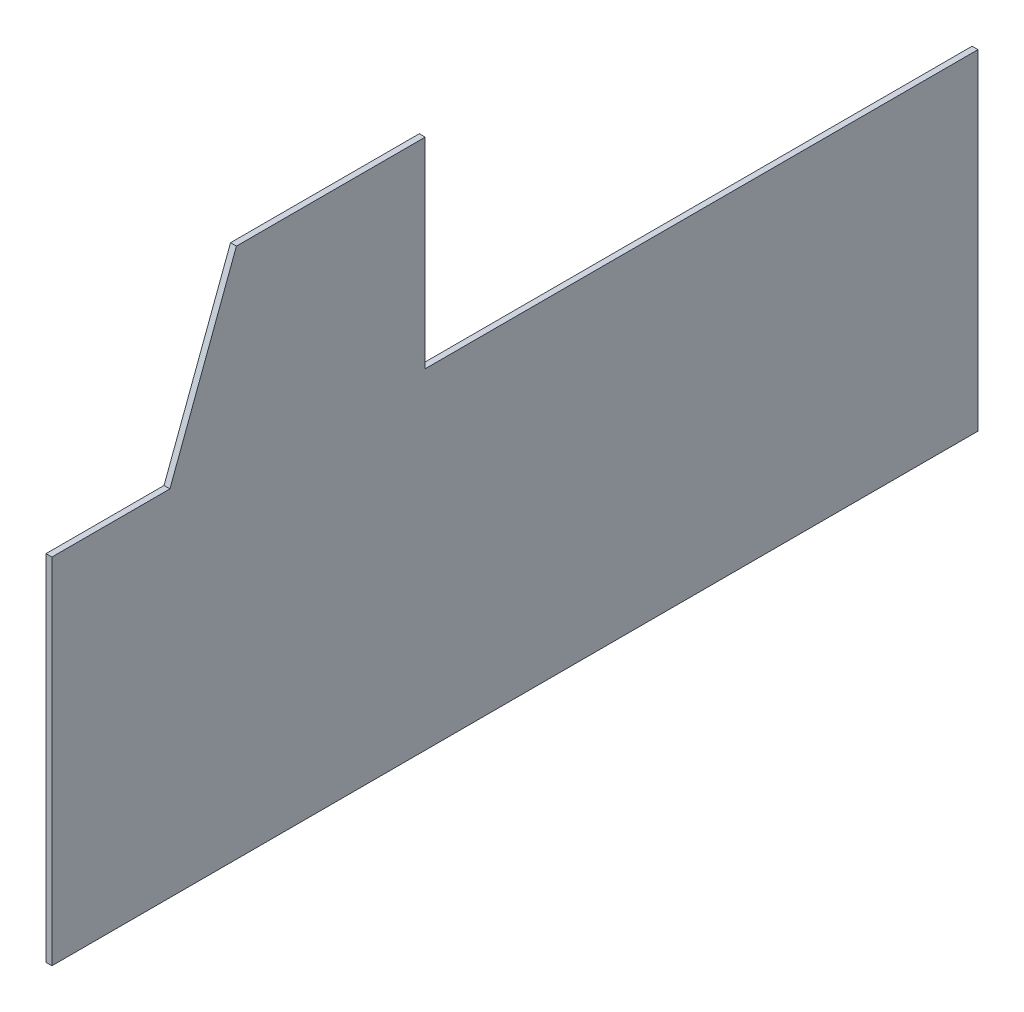
SolidWorks part; units mm, degrees
material "6061-T6 (SS)"
ref_plane "X-Y Datum" through (0, 0, 0) normal (0, 0, 1) x (1, 0, 0)
ref_plane "X-Z Datum" through (0, 0, 0) normal (0, 1, 0) x (1, 0, 0)
ref_plane "Y-Z Datum" through (0, 0, 0) normal (1, 0, 0) x (0, 0, -1)
sketch "Sketch1" plane through (0, 0, 0) normal (1, 0, 0) x (0, 0, -1)
  line L1 (-249.174, 88.9) -> (249.174, 88.9)
  line L2 (-249.174, 88.9) -> (-249.174, -88.9)
  line L3 (-249.174, -88.9) -> (249.174, -88.9)
  line L4 (249.174, 88.9) -> (249.174, -88.9)
  line L5 (-249.174, 88.9) -> (249.174, -88.9) construction
  line L6 (-249.174, -88.9) -> (249.174, 88.9) construction
  point P0 (0, 0)
  dimension "D1" = 177.8
  dimension "D2" = 498.348
extrude "Boss-Extrude1" add sketch "Sketch1" along normal mid plane 3.175
sketch "Sketch2" plane through (-1.5875, 0, 0) normal (-1, 0, 0) x (0, 0, 1)
  line L0 (249.174, 88.9) -> (249.174, -88.9) construction
  line L8 (48.2854, 88.9) -> (249.174, 88.9)
  line L9 (-249.174, 88.9) -> (249.174, 88.9) construction
  line L11 (48.2854, -88.9) -> (48.2854, 76.2)
  line L16 (249.174, 88.9) -> (249.174, 101.6)
  line L17 (249.174, 101.6) -> (185.674, 101.6)
  line L18 (185.674, 101.6) -> (149.8854, 196.85)
  line L19 (149.8854, 196.85) -> (48.2854, 196.85)
  line L20 (48.2854, 196.85) -> (48.2854, 88.9)
  line M14 (249.174, 88.9) -> (-249.174, 88.9)
  dimension "D1" = 12.7
  dimension "D2" = 63.5
  dimension "D4" = 107.95
  dimension "D5" = 101.6
extrude "Boss-Extrude2" add sketch "Sketch2" against normal blind 3.175 contours L19 L20 L16 L17 L18 M14 region at (-1.5875, 137.3997, 115.8494)
